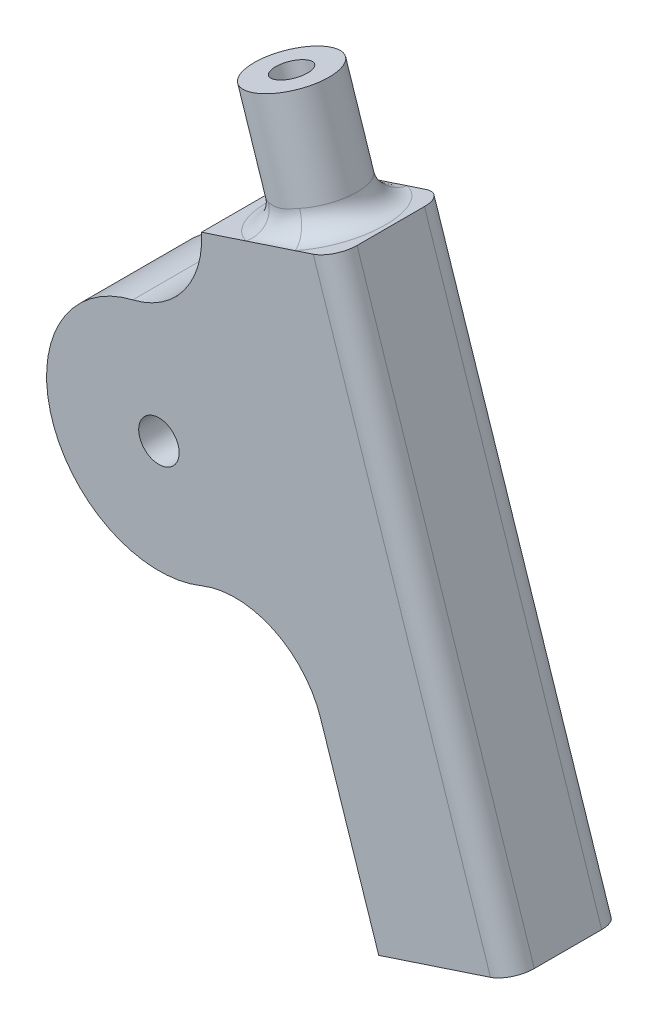
SolidWorks part; units mm, degrees
ref_plane "前视基准面" through (0, 0, 0) normal (0, 0, 1) x (1, 0, 0)
ref_plane "上视基准面" through (0, 0, 0) normal (0, 1, 0) x (1, 0, 0)
ref_plane "右视基准面" through (0, 0, 0) normal (1, 0, 0) x (0, 0, -1)
sketch "草图1" plane through (0, 0, 0) normal (0, 0, 1) x (1, 0, 0)
  circle A0 centre (0, 5.05) radius 2.5
  circle A1 centre (0, 5.05) radius 5
  dimension "D1" = 10
extrude "凸台-拉伸1" add sketch "草图1" against normal blind 2.5
sketch "草图2" plane through (0, 0, 0) normal (0, 0, 1) x (1, 0, 0)
  circle A0 centre (0, 5.05) radius 5
  circle A1 centre (0, 5.05) radius 0.9
extrude "凸台-拉伸2" add sketch "草图2" along normal blind 2.5
sketch "草图3" plane through (0, 0, 2.5) normal (0, 0, 1) x (1, 0, 0)
  line L0 (14.0479, -7.4188) -> (9.4686, -8.9279)
  line L1 (9.4686, -8.9279) -> (1.8963, 14.0502)
  line L2 (1.8963, 14.0502) -> (7.8188, 16.0019)
  line L3 (7.8188, 16.0019) -> (15.3911, -6.9762)
  line L4 (15.3911, -6.9762) -> (14.0479, -7.4188)
extrude "凸台-拉伸3" add sketch "草图3" against normal blind 5
fillet "圆角1" radius 4 2 edges at (3.7859, 8.316, 0) (4.9859, 4.6747, 0)
sketch "草图4" plane through (3.5815, -10.868, 0) normal (0.313, -0.9498, 0) x (0.9498, 0.313, 0)
  circle A0 centre (9.4344, 0) radius 0.75
  dimension "D1" = 1.5
extrude "切除-拉伸1" cut sketch "草图4" against normal blind 28
sketch "草图5" plane through (3.5815, -10.868, 0) normal (0.313, -0.9498, 0) x (0.9498, 0.313, 0)
  line L1 (12.4343, 2.5) -> (6.1985, 2.5)
  line L2 (12.4343, 2.5) -> (12.4343, -2.5)
  line L3 (12.4343, -2.5) -> (6.1985, -2.5)
  line L4 (6.1985, 2.5) -> (6.1985, -2.5)
extrude "凸台-拉伸4" add sketch "草图5" along normal blind 1
sketch "草图6" plane through (-3.9908, 12.1101, 0) normal (-0.313, 0.9498, 0) x (0.9498, 0.313, 0)
  circle A0 centre (9.4344, 0) radius 0.75
  circle A1 centre (9.4344, 0) radius 1.75
extrude "凸台-拉伸5" add sketch "草图6" along normal blind 5
fillet "圆角2" radius 1 1 edges at (3.3075, 14.5153, 0)
fillet "圆角3" radius 1 2 edges at (11.7614, 4.038, -2.5) (11.7614, 4.038, 2.5)
